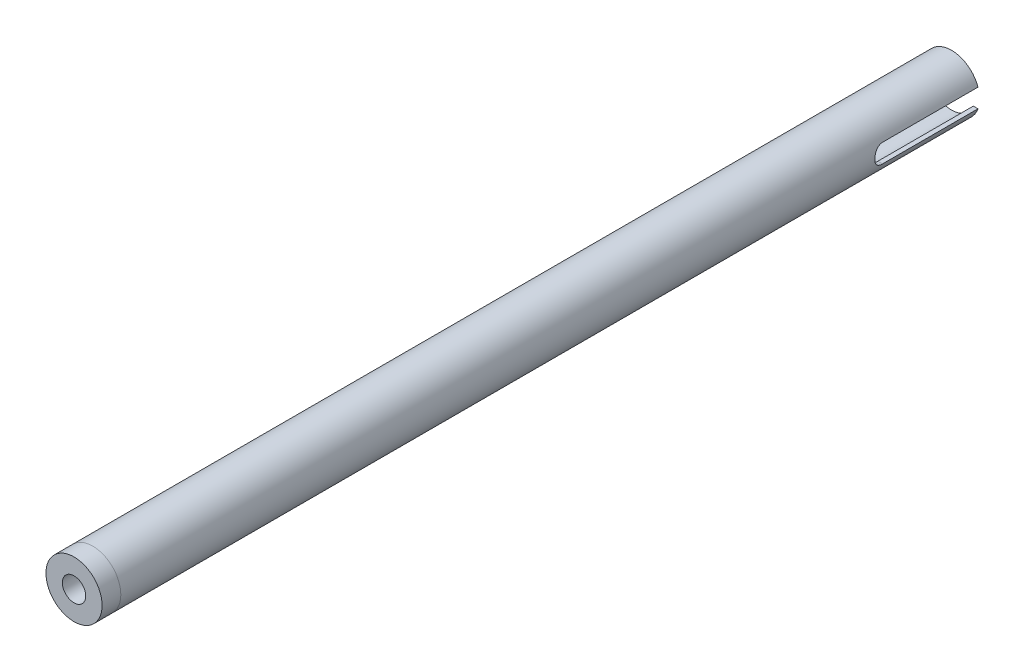
SolidWorks part; units mm, degrees
material "AISI 4130 Steel, normalized at 870C"
ref_plane "Front Plane" through (0, 0, 0) normal (0, 0, 1) x (1, 0, 0)
ref_plane "Top Plane" through (0, 0, 0) normal (0, 1, 0) x (1, 0, 0)
ref_plane "Right Plane" through (0, 0, 0) normal (1, 0, 0) x (0, 0, -1)
sketch "Axis" plane through (0, 0, 0) normal (0, 1, 0) x (1, 0, 0)
  line L0 (0, 0) -> (0, 297.7126) construction
  line L1 (0, 0) -> (0, -28.575) construction
  line L2 (0, 297.7126) -> (-9.525, 297.7126) construction
  line L3 (0, 325.6526) -> (-31.298, 233.8452) construction
  dimension "D1" = 28.575
  dimension "D2" = 9.525
sketch "Sketch1" plane through (0, 0, 0) normal (0, 0, 1) x (1, 0, 0)
  line L0 (-9.525, 0) -> (9.525, 0) construction
  line L1 (-8.9803, 3.175) -> (8.9803, 3.175)
  line L2 (-8.9803, -3.175) -> (8.9803, -3.175)
  circle A0 centre (0, 0) radius 9.525
  circle A1 centre (0, 0) radius 8.0518
  circle A2 centre (0, 0) radius 3.9688
  dimension "D1" = 19.05
  dimension "D3" = 7.9375
  dimension "D2" = 1.4732
  dimension "D4" = 6.35
extrude "Threaded insert 1-1" add sketch "Sketch1" against normal blind 6.35 contours A2 L1 A1 | A1 L1 A0 | A2 L0 A1 L1 | A1 L0 A0 L1 | L0 A1 L2 A0 | L0 A2 L2 A1 | A2 L2 A1 | A1 L2 A0 | L0 A1 L2 A2 | L0 A0 L2 A1 | A0 L0 A1 L1 | A1 L0 A2 L1 region at (5.645, 1.6393, 0) region at (5.645, -1.6393, 0) region at (8.588, 1.606, 0) region at (8.588, -1.606, 0) region at (-5.645, -1.6393, 0) region at (-5.645, 1.6393, 0) region at (0, 5.2753, 0) region at (0, -5.2753, 0) region at (0, 8.2423, 0) region at (8.1898, -3.3655, 0) region at (-8.588, -1.606, 0) region at (-8.588, 1.606, 0)
extrude "Threaded insert 1-2" add sketch "Sketch1<3>" against normal blind 9.525 from surface contours A2 L1 A1 | A2 L0 A1 L1 | L0 A2 L2 A1 | A2 L2 A1 | L0 A1 L2 A2 | A1 L0 A2 L1 region at (5.645, 1.6393, 0) region at (5.645, -1.6393, 0) region at (-5.645, -1.6393, 0) region at (-5.645, 1.6393, 0) region at (0, 5.2753, 0) region at (0, -5.2753, 0) starting at face at (9.525, 0, -6.35)
sketch "Sketch1<3>" plane through (0, 0, 0) normal (0, 0, 1) x (1, 0, 0) same geometry as "Sketch1"
extrude "A-arm tube" add sketch "Sketch1<4>" against normal up to vertex (297.7126 mm away) from surface separate body contours A1 L1 A0 | A1 L0 A0 L1 | L0 A1 L2 A0 | A1 L2 A0 | L0 A0 L2 A1 | A0 L0 A1 L1 region at (8.588, 1.606, 0) region at (8.588, -1.606, 0) region at (0, 8.2423, 0) region at (8.1898, -3.3655, 0) region at (-8.588, -1.606, 0) region at (-8.588, 1.606, 0) up to point (0, 0, -297.7126) starting at face at (8.0518, 0, -6.35)
sketch "Sketch1<4>" plane through (0, 0, 0) normal (0, 0, 1) x (1, 0, 0) same geometry as "Sketch1"
extrude "Apex slot" cut sketch "Sketch1<5>" along normal blind 35.56 from surface contours A0 L0 A1 L1 | L0 A0 L2 A1 | A1 L0 A0 L1 | L0 A1 L2 A0 region at (8.588, 1.606, 0) region at (8.588, -1.606, 0) region at (-8.588, -1.606, 0) region at (-8.588, 1.606, 0) starting at face at (8.0518, 0, -297.7126)
sketch "Sketch1<5>" plane through (0, 0, 0) normal (0, 0, 1) x (1, 0, 0) same geometry as "Sketch1"
fillet "Fillet1" radius 3.175 4 edges at (-8.1898, 3.175, -262.1526) (-8.1898, -3.175, -262.1526) (8.1898, -3.175, -262.1526) (8.1898, 3.175, -262.1526)
equation "\"tube diameter\"= .75"
equation "\"tube thickness\"= .058"
equation "\"apex thickness\"= .25"
equation "\"tube slot\"= 1.4"
equation "\"D1@Sketch1\"=\"tube diameter\""
equation "\"D2@Sketch1\"=\"tube thickness\""
equation "\"threaded insert hole\"= .3125"
equation "\"D3@Sketch1\"=\"threaded insert hole\""
equation "\"D4@Sketch1\"=\"apex thickness\""
equation "\"D1@Apex slot\" = \"tube slot\""
equation "\"D1@Fillet1\"=\"apex thickness\"/2"
equation "\"D2@Axis\"=\"tube diameter\"/2"
